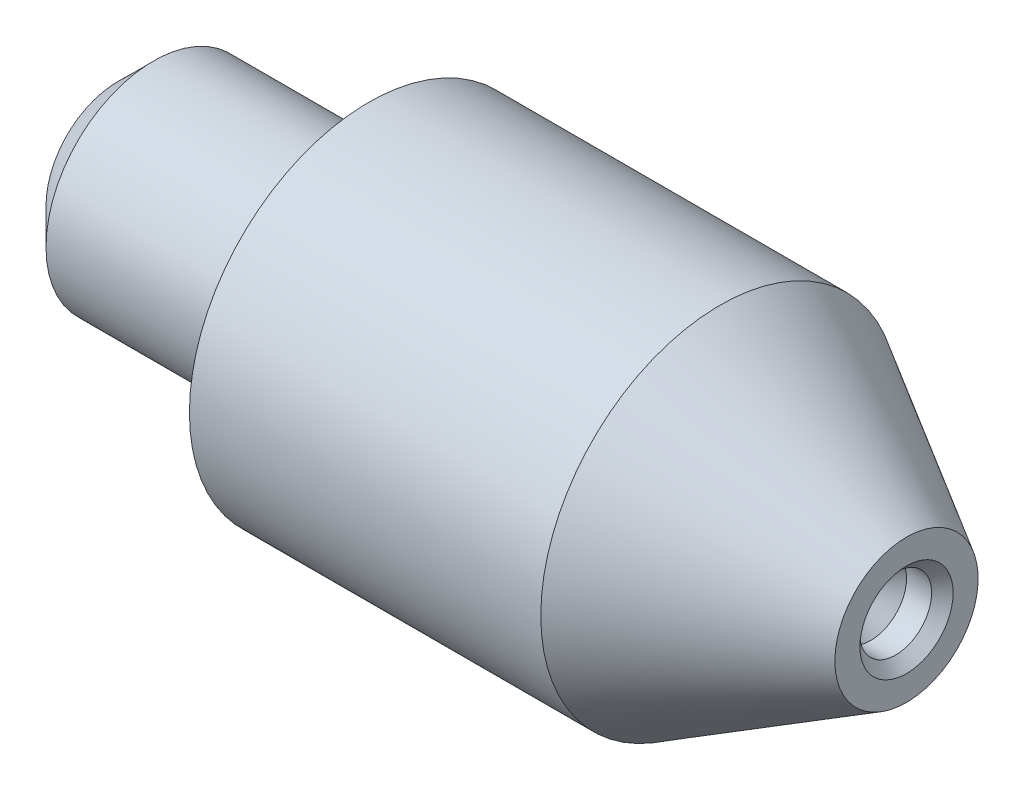
SolidWorks part; units mm, degrees
material "7075-T6 (SN)"
ref_plane "Front Plane" through (0, 0, 0) normal (0, 0, 1) x (1, 0, 0)
ref_plane "Top Plane" through (0, 0, 0) normal (0, 1, 0) x (1, 0, 0)
ref_plane "Right Plane" through (0, 0, 0) normal (1, 0, 0) x (0, 0, -1)
sketch "Sketch1" plane through (0, 0, 0) normal (0, 1, 0) x (1, 0, 0)
  line L0 (-2.8453, 0) -> (6.0462, 0) construction
  line L1 (-7, 0) -> (-7, 2)
  line L2 (-7, 2) -> (-6, 3)
  line L3 (-6, 3) -> (0, 3)
  line L4 (0, 3) -> (0, 5)
  line L5 (0, 5) -> (9.8, 5)
  line L6 (9.8, 5) -> (15, 1.9978)
  line L7 (15, 1.9978) -> (15, 0)
  line L8 (-7, 0) -> (15, 0)
  dimension "D1" = 22
  dimension "D2" = 1
  dimension "D3" = 1
  dimension "D4" = 3
  dimension "D5" = 5
  dimension "D6" = 15
  dimension "D7" = 5.2
  dimension "D8" = 30
revolve "Revolve1" add sketch "Sketch1" angle 360 about L0
sketch "Sketch2" plane through (15, 0, 0) normal (1, 0, 0) x (0, 0, -1)
  circle A0 centre (0, 0) radius 1
  dimension "D1" = 2
extrude "Cut-Extrude1" cut sketch "Sketch2" against normal blind 0.3
chamfer "Chamfer1" distance 0.3 angle 45 1 edges at (15, 0, -1)
sketch "Sketch3" plane through (14.7, 0, 0) normal (1, 0, 0) x (0, 0, -1)
  circle A1 centre (0, 0) radius 1
  circle A2 centre (0, 0) radius 1
  dimension "D1" = 0
extrude "Cut-Extrude2" cut sketch "Sketch3" against normal blind 0.7
sketch "Sketch4" plane through (14, 0, 0) normal (1, 0, 0) x (0, 0, -1)
  circle A1 centre (0, 0) radius 1
  circle A2 centre (0, 0) radius 1
  dimension "D1" = 0
extrude "Cut-Extrude3" cut sketch "Sketch4" against normal blind 1 draft 45
